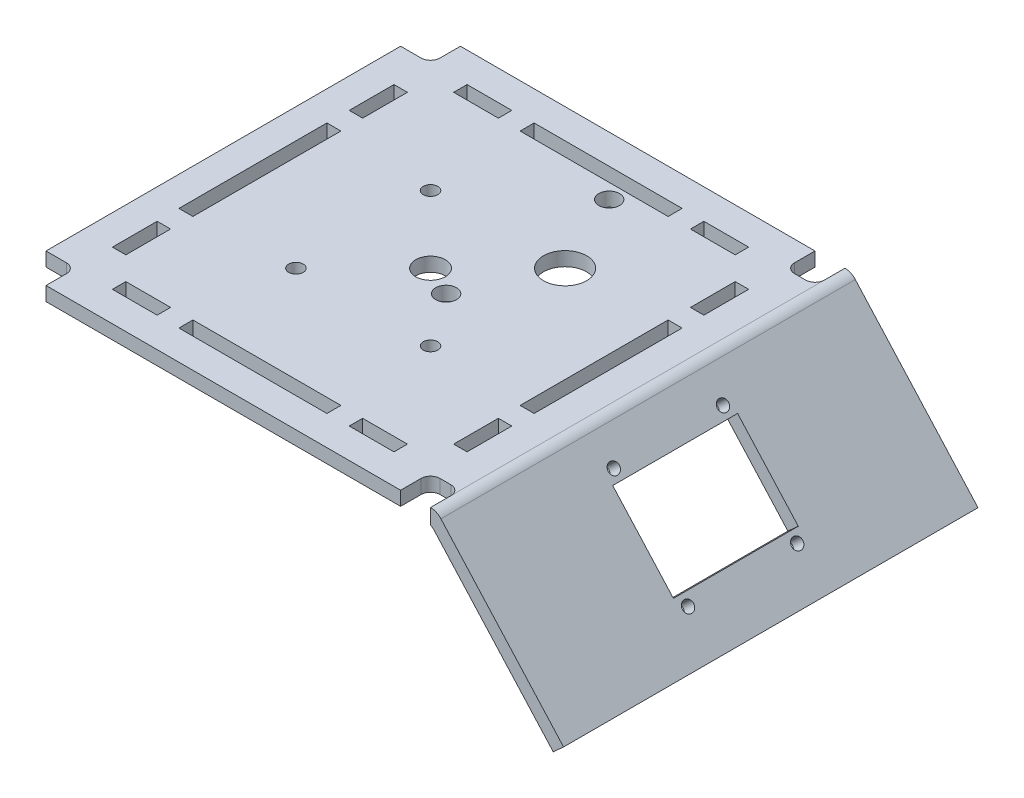
SolidWorks part; units mm, degrees
material "Acrylic (Medium-high impact)"
ref_plane "Front Plane" through (0, 0, 0) normal (0, 0, 1) x (1, 0, 0)
ref_plane "Top Plane" through (0, 0, 0) normal (0, 1, 0) x (1, 0, 0)
ref_plane "Right Plane" through (0, 0, 0) normal (1, 0, 0) x (0, 0, -1)
sketch "스케치2" plane through (0, 0, 0) normal (0, 0, 1) x (1, 0, 0)
  line L0 (44.45, -1.5) -> (46.6794, 0.5074) construction
  line L1 (-44.45, 1.5) -> (44.45, 1.5)
  line L2 (-44.45, 1.5) -> (-44.45, -1.5)
  line L3 (-44.45, -1.5) -> (44.45, -1.5)
  line L4 (44.45, 1.5) -> (44.45, -1.5) construction
  line L5 (-44.45, 1.5) -> (44.45, -1.5) construction
  line L6 (-44.45, -1.5) -> (44.45, 1.5) construction
  line L7 (44.45, -1.5) -> (68.7609, -28.5)
  line L8 (46.6794, 0.5074) -> (70.9903, -26.4926)
  line L9 (68.7609, -28.5) -> (70.9903, -26.4926)
  line L10 (44.45, -1.5) -> (44.45, -28.5)
  line L11 (44.45, -28.5) -> (68.7609, -28.5) construction
  arc A0 (44.45, 1.5) -> (46.6794, 0.5074) centre (44.45, -1.5) cw
  point P0 (0, 0)
  dimension "D1" = 3
  dimension "D2" = 88.9
  dimension "D3" = 48
  dimension "D4" = 3
  dimension "30mm" = 30
extrude "보스-돌출1" add sketch "스케치2" along normal blind 88.9 contours A0 L1 L2 L3 L7 L9 L8 region at (0, 0.3073, 0)
sketch "스케치3" plane through (44.9587, -49.9316, 0) normal (0.6691, -0.7431, 0) x (0.7431, 0.6691, 0)
  line L4 (32.0291, 0) -> (35.0291, 0)
  line L5 (35.0291, 0) -> (35.0291, 88.9)
  line L6 (35.0291, 88.9) -> (32.0291, 88.9)
  line L7 (32.0291, 88.9) -> (32.0291, 0)
  line L8 (32.0291, 0) -> (35.0291, 0)
  line L9 (35.0291, 0) -> (35.0291, 88.9)
  line L10 (35.0291, 88.9) -> (32.0291, 88.9)
  line L11 (32.0291, 88.9) -> (32.0291, 0)
  dimension "D1" = 0
extrude "보스-돌출2" add sketch "스케치3" along normal blind 3
sketch "스케치4" plane through (0, 1.5, 0) normal (0, 1, 0) x (1, 0, 0)
  line L0 (-44.45, -88.9) -> (-44.45, 0) construction
  line L1 (-44.45, -88.9) -> (44.45, -88.9) construction
  line L2 (-44.45, -88.9) -> (-44.45, 0) construction
  line L3 (-44.45, 0) -> (44.45, 0) construction
  line L4 (44.45, -88.9) -> (44.45, 0) construction
  line L5 (-44.45, -88.9) -> (44.45, 0) construction
  line L6 (-44.45, 0) -> (44.45, -88.9) construction
  line L7 (-44.45, 0) -> (44.45, 0) construction
  line L8 (-38.1, -82.55) -> (-44.45, -88.9) construction
  line L9 (-38.1, -82.55) -> (38.1, -82.55) construction
  line L10 (-38.1, -82.55) -> (-38.1, -6.35) construction
  line L11 (-38.1, -6.35) -> (38.1, -6.35) construction
  line L12 (38.1, -82.55) -> (38.1, -6.35) construction
  line L13 (-38.1, -82.55) -> (38.1, -6.35) construction
  line L14 (-38.1, -6.35) -> (38.1, -82.55) construction
  line L15 (44.45, 0) -> (38.1, -6.35) construction
  line L16 (0, -44.45) -> (0, -81.05) construction
  line L17 (-15.875, -79.55) -> (15.875, -79.55)
  line L18 (-15.875, -79.55) -> (-15.875, -82.55)
  line L19 (-15.875, -82.55) -> (15.875, -82.55)
  line L20 (15.875, -79.55) -> (15.875, -82.55)
  line L21 (-15.875, -79.55) -> (15.875, -82.55) construction
  line L22 (-15.875, -82.55) -> (15.875, -79.55) construction
  line L23 (-35.1, -28.575) -> (-38.1, -28.575)
  line L24 (-35.1, -28.575) -> (-35.1, -60.325)
  line L25 (-35.1, -60.325) -> (-38.1, -60.325)
  line L26 (-38.1, -28.575) -> (-38.1, -60.325)
  line L27 (15.875, -9.35) -> (15.875, -6.35)
  line L28 (15.875, -9.35) -> (-15.875, -9.35)
  line L29 (-15.875, -9.35) -> (-15.875, -6.35)
  line L30 (15.875, -6.35) -> (-15.875, -6.35)
  line L31 (35.1, -60.325) -> (38.1, -60.325)
  line L32 (35.1, -60.325) -> (35.1, -28.575)
  line L33 (35.1, -28.575) -> (38.1, -28.575)
  line L34 (38.1, -60.325) -> (38.1, -28.575)
  line L35 (0, -9.35) -> (0, -44.45) construction
  line L36 (-35.1, -44.45) -> (0, -44.45) construction
  line L37 (0, -44.45) -> (0, -9.35) construction
  line L38 (0, -44.45) -> (35.1, -44.45) construction
  circle A0 centre (-41.275, -85.725) radius 1.5
  circle A1 centre (-41.275, -3.175) radius 1.5
  circle A2 centre (41.275, -3.175) radius 1.5
  circle A3 centre (41.275, -85.725) radius 1.5
  point P0 (0, -44.45)
  point P13 (0, -44.45)
  point P19 (0, -81.05)
  point P27 (0, -44.45)
  point P47 (0, -44.45)
  dimension "D3" = 3
  dimension "D1" = 76.2
  dimension "D2" = 76.2
  dimension "D5" = 3
  dimension "D6" = 31.75
  dimension "D8" = 35.1
  dimension "D4" = 4
extrude "컷-돌출1" cut sketch "스케치4" against normal up to surface (3 mm away) up to face at (0, -1.5, 44.45)
sketch "스케치5" plane through (0, 1.5, 0) normal (0, 1, 0) x (1, 0, 0)
  line L0 (0, 0) -> (0, -88.9) construction
  line L1 (-44.45, -88.9) -> (44.45, -88.9) construction
  line L2 (-44.45, -44.45) -> (44.45, -44.45) construction
  line L3 (-44.45, -88.9) -> (-44.45, 0) construction
  line L4 (44.45, -88.9) -> (44.45, 0) construction
  circle A0 centre (-14.4318, -30.0182) radius 15.875 construction
  circle A1 centre (-14.4318, -30.0182) radius 12.827 construction
  circle A2 centre (-14.4318, -30.0182) radius 1.56
  circle A3 centre (14.4318, -30.0182) radius 12.827 construction
  circle A4 centre (14.4318, -30.0182) radius 15.875 construction
  circle A5 centre (14.4318, -30.0182) radius 1.56
  circle A6 centre (14.4318, -58.8818) radius 12.827 construction
  circle A7 centre (14.4318, -58.8818) radius 15.875 construction
  circle A8 centre (14.4318, -58.8818) radius 1.56
  circle A9 centre (-14.4318, -58.8818) radius 12.827 construction
  circle A10 centre (-14.4318, -58.8818) radius 15.875 construction
  circle A11 centre (-14.4318, -58.8818) radius 1.56
  point P8 (0, -44.45)
  point P9 (-14.4318, -30.0182)
  point P10 (-1.6048, -30.0182)
  point P14 (-14.4318, -42.8452)
  point P34 (0, -44.45)
  dimension "D1" = 31.75
  dimension "D2" = 25.654
  dimension "D5" = 3.12
  dimension "D3" = 28.8636
  dimension "D4" = 28.8636
  dimension "D6" = 4
extrude "컷-돌출2" cut sketch "스케치5" against normal up to surface (3 mm away) up to face at (0, -1.5, 81.05)
sketch "스케치7" plane through (0, 1.5, 0) normal (0, 1, 0) x (1, 0, 0)
  line L0 (22.4618, -12.5282) -> (22.4618, -47.5082) construction
  line L1 (14.4318, -30.0182) -> (22.4618, -30.0182) construction
  line L2 (14.4318, -30.0182) -> (14.4318, -9.35) construction
  line L3 (-15.875, -9.35) -> (15.875, -9.35) construction
  circle A0 centre (14.4318, -30.0182) radius 4.635
  circle A1 centre (22.4618, -12.5282) radius 2.23 construction
  circle A2 centre (22.4618, -47.5082) radius 2.23 construction
  circle A3 centre (14.4318, -30.0182) radius 1.56 construction
  circle A4 centre (22.4618, -30.0182) radius 14.045 construction
  circle A6 centre (14.4318, -30.0182) radius 15.875 construction
  circle A7 centre (14.4318, -58.8818) radius 15.875 construction
  circle A8 centre (6.4018, -47.5082) radius 2.23
  circle A9 centre (6.4018, -12.5282) radius 2.23
  point P7 (9.7968, -30.0182)
  point P8 (8.4168, -30.0182)
  dimension "D1" = 9.27
  dimension "D2" = 4.46
  dimension "D4" = 28.09
  dimension "D6" = 31.75
  dimension "D3" = 34.98
  dimension "D5" = 1.38
extrude "컷-돌출3" cut sketch "스케치7" against normal up to surface (3 mm away) up to face at (-14.4318, -1.5, 60.4418)
sketch "스케치8" plane through (0, 1.5, 0) normal (0, 1, 0) x (1, 0, 0)
  line L0 (-44.45, -88.9) -> (44.45, -88.9) construction
  line L1 (-30.2, -9.35) -> (-20.6, -9.35) construction
  line L2 (-30.2, -9.35) -> (-30.2, -6.35) construction
  line L3 (-30.2, -6.35) -> (-20.6, -6.35) construction
  line L4 (-20.6, -9.35) -> (-20.6, -6.35) construction
  line L5 (-30.2, -9.35) -> (-20.6, -6.35) construction
  line L6 (-30.2, -6.35) -> (-20.6, -9.35) construction
  line L7 (44.45, -88.9) -> (-44.45, -88.9) construction
  line L8 (44.45, -88.9) -> (44.45, 0) construction
  line L9 (44.45, 0) -> (-44.45, 0) construction
  line L10 (-44.45, -88.9) -> (-44.45, 0) construction
  line L11 (44.45, -88.9) -> (-44.45, 0) construction
  line L12 (44.45, 0) -> (-44.45, -88.9) construction
  line L13 (44.45, -88.9) -> (44.45, 0) construction
  line L14 (-38.1, -28.575) -> (-38.1, -6.35) construction
  line L15 (-38.1, -6.35) -> (38.1, -6.35) construction
  line L16 (0, -44.45) -> (0, -6.35) construction
  line L17 (-30.2, -9.29) -> (-20.6, -9.29)
  line L18 (-30.2, -9.29) -> (-30.2, -6.41)
  line L19 (-30.2, -6.41) -> (-20.6, -6.41)
  line L20 (-20.6, -9.29) -> (-20.6, -6.41)
  line L21 (-30.2, -9.29) -> (-20.6, -6.41) construction
  line L22 (-30.2, -6.41) -> (-20.6, -9.29) construction
  line L23 (-35.1, -14.25) -> (-38.1, -14.25) construction
  line L24 (-35.1, -14.25) -> (-35.1, -23.85) construction
  line L25 (-35.1, -23.85) -> (-38.1, -23.85) construction
  line L26 (-38.1, -14.25) -> (-38.1, -23.85) construction
  line L27 (-35.1, -14.25) -> (-38.1, -23.85) construction
  line L28 (-35.1, -23.85) -> (-38.1, -14.25) construction
  line L29 (-38.04, -23.85) -> (-35.16, -23.85)
  line L30 (-38.04, -23.85) -> (-38.04, -14.25)
  line L31 (-38.04, -14.25) -> (-35.16, -14.25)
  line L32 (-35.16, -23.85) -> (-35.16, -14.25)
  line L33 (-38.04, -23.85) -> (-35.16, -14.25) construction
  line L34 (-38.04, -14.25) -> (-35.16, -23.85) construction
  line L35 (0, -44.45) -> (44.45, -44.45) construction
  line L36 (38.04, -23.85) -> (35.16, -23.85)
  line L37 (35.16, -23.85) -> (35.16, -14.25)
  line L38 (38.04, -23.85) -> (38.04, -14.25)
  line L39 (38.04, -14.25) -> (35.16, -14.25)
  line L40 (20.6, -9.29) -> (20.6, -6.41)
  line L41 (30.2, -6.41) -> (20.6, -6.41)
  line L42 (30.2, -9.29) -> (20.6, -9.29)
  line L43 (30.2, -9.29) -> (30.2, -6.41)
  line L44 (38.04, -65.05) -> (35.16, -65.05)
  line L45 (38.04, -65.05) -> (38.04, -74.65)
  line L46 (38.04, -74.65) -> (35.16, -74.65)
  line L47 (35.16, -65.05) -> (35.16, -74.65)
  line L48 (20.6, -79.61) -> (20.6, -82.49)
  line L49 (30.2, -79.61) -> (20.6, -79.61)
  line L50 (30.2, -82.49) -> (20.6, -82.49)
  line L51 (30.2, -79.61) -> (30.2, -82.49)
  line L52 (-30.2, -79.61) -> (-20.6, -79.61)
  line L53 (-30.2, -82.49) -> (-20.6, -82.49)
  line L54 (-30.2, -79.61) -> (-30.2, -82.49)
  line L55 (-20.6, -79.61) -> (-20.6, -82.49)
  line L56 (-38.04, -65.05) -> (-35.16, -65.05)
  line L57 (-38.04, -74.65) -> (-35.16, -74.65)
  line L58 (-38.04, -65.05) -> (-38.04, -74.65)
  line L59 (-35.16, -65.05) -> (-35.16, -74.65)
  point P0 (-25.4, -7.85)
  point P5 (0, -44.45)
  point P18 (-36.6, -19.05)
  point P20 (-25.4, -7.85)
  point P29 (-36.6, -19.05)
  dimension "D1" = 3
  dimension "D2" = 25.4
  dimension "D3" = 2.88
  dimension "D4" = 9.6
  dimension "D5" = 3
  dimension "D6" = 9.6
  dimension "D7" = 25.4
  dimension "D8" = 2.88
extrude "컷-돌출4" cut sketch "스케치8" against normal up to surface (3 mm away) up to face at (14.4318, -1.5, 34.6532)
sketch "스케치9" plane through (0, 1.5, 0) normal (0, 1, 0) x (1, 0, 0)
  line L1 (44.45, -88.9) -> (-44.45, -88.9) construction
  line L2 (44.45, -88.9) -> (44.45, 0) construction
  line L3 (44.45, 0) -> (-44.45, 0) construction
  line L4 (-44.45, -88.9) -> (-44.45, 0) construction
  line L5 (44.45, -88.9) -> (-44.45, 0) construction
  line L6 (44.45, 0) -> (-44.45, -88.9) construction
  circle A0 centre (0, -44.45) radius 3.175
  point P0 (0, -44.45)
  dimension "D1" = 6.35
extrude "컷-돌출5" cut sketch "스케치9" against normal up to surface (3 mm away) up to face at (36.6, -1.5, 69.85)
sketch "스케치11" plane through (26.0317, 23.439, 0) normal (0.7431, 0.6691, 0) x (0, 0, -1)
  line L0 (-44.45, -49.2536) -> (-44.45, -70.1897) construction
  line L1 (-58.1422, -63.1442) -> (-30.7578, -63.1442) construction
  line L2 (-58.1422, -63.1442) -> (-58.1422, -35.363) construction
  line L3 (-58.1422, -35.363) -> (-30.7578, -35.363) construction
  line L4 (-30.7578, -63.1442) -> (-30.7578, -35.363) construction
  line L5 (-58.1422, -63.1442) -> (-30.7578, -35.363) construction
  line L6 (-58.1422, -35.363) -> (-30.7578, -63.1442) construction
  line L7 (0, -70.1897) -> (-88.9, -70.1897) construction
  line L8 (0, -50.5236) -> (-88.9, -50.5236) construction
  line L9 (-44.45, -49.2536) -> (-31.0555, -49.2536) construction
  line L10 (-58.1422, -37.3474) -> (-56.1578, -37.3474) construction
  line L11 (-57.8445, -39.5302) -> (-31.0555, -39.5302)
  line L12 (-57.8445, -39.5302) -> (-57.8445, -58.9771)
  line L13 (-57.8445, -58.9771) -> (-31.0555, -58.9771)
  line L14 (-31.0555, -39.5302) -> (-31.0555, -58.9771)
  line L15 (-57.8445, -39.5302) -> (-31.0555, -58.9771) construction
  line L16 (-57.8445, -58.9771) -> (-31.0555, -39.5302) construction
  line L17 (-56.1578, -37.3474) -> (-56.1578, -35.363) construction
  line L18 (0, -30.8576) -> (0, -70.1897) construction
  line L19 (-88.9, -30.8576) -> (-88.9, -70.1897) construction
  line L20 (-88.9, -30.8576) -> (-88.9, -70.1897) construction
  circle A0 centre (-56.1578, -37.3474) radius 1.1906
  circle A1 centre (-56.1578, -37.3474) radius 1.8852 construction
  circle A2 centre (-32.7422, -37.3474) radius 1.1906
  circle A3 centre (-32.7422, -61.1599) radius 1.1906
  circle A4 centre (-56.1578, -61.1599) radius 1.1906
  point P0 (-44.45, -49.2536)
  dimension "D6" = 2.3813
  dimension "D7" = 3.7703
  dimension "D8" = 1.27
  dimension "D1" = 27.3844
  dimension "D2" = 27.7812
  dimension "D3" = 26.7891
  dimension "D4" = 19.4469
  dimension "D5" = 1.9844
  dimension "D9" = 39.3321
  dimension "D10" = 11.2126
extrude "컷-돌출6" cut sketch "스케치11" against normal up to surface (3 mm away) up to face at (57.6092, -16.1147, 44.45)
fillet "필렛1" radius 2.54 1 edges at (44.45, -1.5, 44.45)
sketch "스케치12" plane through (0, 1.5, 0) normal (0, 1, 0) x (1, 0, 0)
  line L1 (-41.275, -82.5496) -> (-44.025, -84.1373)
  line L2 (-44.025, -84.1373) -> (-44.025, -87.3127)
  line L3 (-44.025, -87.3127) -> (-41.275, -88.9004)
  line L4 (-41.275, -88.9004) -> (-38.525, -87.3127)
  line L5 (-38.525, -87.3127) -> (-38.525, -84.1373)
  line L6 (-38.525, -84.1373) -> (-41.275, -82.5496)
  circle A0 centre (-41.275, -85.725) radius 2.75
  circle A1 centre (-41.275, -85.725) radius 1.5 construction
  circle A2 centre (-41.275, -85.725) radius 2.75 construction
  dimension "D1" = 5.5
sketch "스케치13" plane through (0, 1.5, 0) normal (0, 1, 0) x (1, 0, 0)
  line L0 (-38.04, -74.65) -> (-38.04, -82.49) construction
  line L1 (-44.45, -88.9) -> (-38.0365, -88.9)
  line L2 (-44.45, -88.9) -> (-44.45, -82.4865)
  line L3 (-44.45, -82.4865) -> (-38.0365, -82.4865)
  line L4 (-38.0365, -88.9) -> (-38.0365, -82.4865)
  line L5 (-44.45, -88.9) -> (-38.0365, -82.4865) construction
  line L6 (-44.45, -82.4865) -> (-38.0365, -88.9) construction
  line L7 (-38.04, -82.49) -> (-30.2, -82.49) construction
  line L8 (-44.45, 0) -> (-38.0365, 0)
  line L9 (-44.45, 0) -> (-44.45, -6.4135)
  line L10 (-44.45, -6.4135) -> (-38.0365, -6.4135)
  line L11 (-38.0365, 0) -> (-38.0365, -6.4135)
  line L12 (44.45, 0) -> (44.45, -6.4135)
  line L13 (44.45, 0) -> (38.0365, 0)
  line L14 (38.0365, 0) -> (38.0365, -6.4135)
  line L15 (44.45, -6.4135) -> (38.0365, -6.4135)
  line L16 (44.45, -88.9) -> (38.0365, -88.9)
  line L17 (44.45, -88.9) -> (44.45, -82.4865)
  line L18 (44.45, -82.4865) -> (38.0365, -82.4865)
  line L19 (38.0365, -88.9) -> (38.0365, -82.4865)
  point P4 (-41.2432, -85.6932)
  point P14 (0, -44.45)
  point P28 (0, -44.45)
  dimension "D1" = 6.4135
  dimension "D2" = 4
extrude "컷-돌출7" cut sketch "스케치13" against normal blind 5.08
sketch "스케치14" plane through (0, 1.5, 0) normal (0, 1, 0) x (1, 0, 0)
  circle A0 centre (-41.275, -85.725) radius 3.1754 construction
fillet "필렛2" radius 2.032 6 edges at (38.0365, 0, 6.4135) (44.45, -0.1328, 6.4135) (-38.0365, 0, 6.4135) (44.45, -0.1328, 82.4865) (38.0365, 0, 82.4865) (-38.0365, 0, 82.4865)
sketch "스케치15" plane through (26.0317, 23.439, 0) normal (0.7431, 0.6691, 0) x (0, 0, -1)
  line L0 (-88.9, -30.8576) -> (-88.9, -70.1897) construction
  line L1 (-88.9, -30.8576) -> (-88.9, -70.1897)
  dimension "D1" = 39.3321
